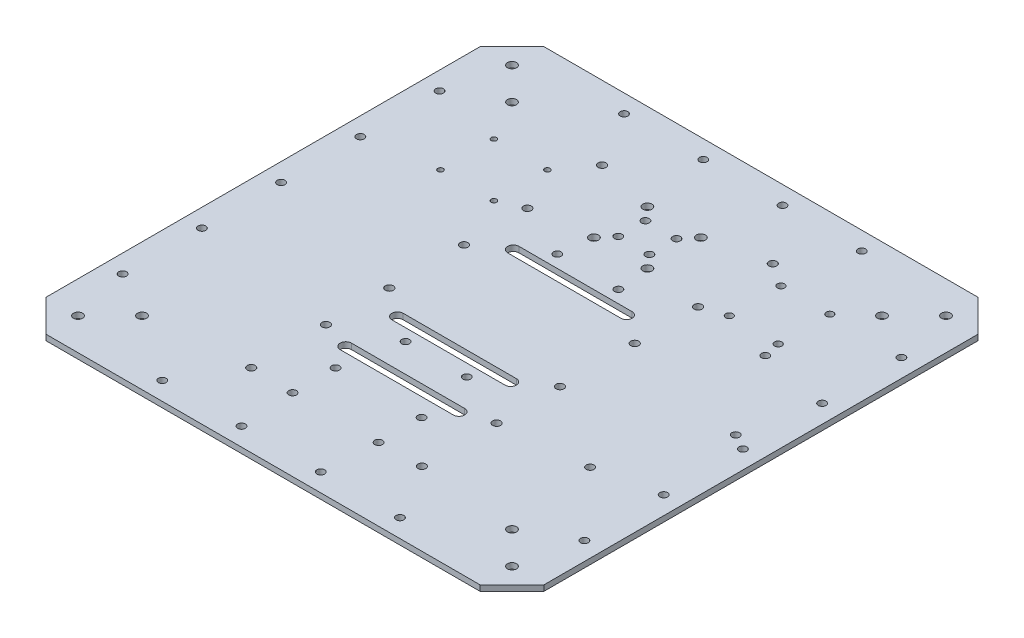
SolidWorks part; units mm, degrees
ref_plane "Front Plane" through (0, 0, 0) normal (0, 0, 1) x (1, 0, 0)
ref_plane "Top Plane" through (0, 0, 0) normal (0, 1, 0) x (1, 0, 0)
ref_plane "Right Plane" through (0, 0, 0) normal (1, 0, 0) x (0, 0, -1)
sketch "Sketch1" plane through (0, 0, 0) normal (0, 1, 0) x (1, 0, 0)
  line L0 (-160.4847, 61.5307) -> (-142.5242, 79.4912)
  line L1 (-160.4847, 79.4912) -> (118.9153, 79.4912)
  line L2 (-160.4847, 79.4912) -> (-160.4847, -199.9088)
  line L3 (-160.4847, -199.9088) -> (118.9153, -199.9088)
  line L4 (118.9153, 79.4912) -> (118.9153, -199.9088)
  line L5 (-20.7847, 79.4912) -> (-20.7847, -199.9088) construction
  line L6 (-160.4847, -60.2088) -> (118.9153, -60.2088) construction
  line L7 (118.9153, 61.5307) -> (100.9548, 79.4912)
  line L8 (118.9153, -181.9483) -> (100.9548, -199.9088)
  line L9 (-160.4847, -181.9483) -> (-142.5242, -199.9088)
  line L10 (-268.2478, 187.2542) -> (226.6783, -307.6719) construction
  line L11 (226.6783, -307.6719) -> (226.6783, 187.2542) construction
  line L12 (226.6783, 187.2542) -> (-268.2478, -307.6719) construction
  line L13 (-268.2478, -307.6719) -> (-268.2478, 187.2542) construction
  line L14 (-268.2478, 187.2542) -> (226.6783, 187.2542) construction
  line L15 (-268.2478, -307.6719) -> (226.6783, -307.6719) construction
  line L16 (-151.5045, 70.5109) -> (-268.2478, 187.2542) construction
  point P8 (-20.7847, 79.4912)
  point P11 (-160.4847, -60.2088)
  point P19 (118.9153, -60.2088)
  point P20 (-20.7847, -199.9088)
  point P22 (-151.5045, 70.5109)
  point P25 (-20.7847, -60.2088)
  point P26 (-20.7847, -60.2088)
  dimension "D1" = 279.4
  dimension "D2" = 279.4
  dimension "D3" = 165.1
  dimension "D4" = 25.4
extrude "Boss-Extrude1" add sketch "Sketch1" along normal blind 3.175 contours L2 L9 L3 L8 L4 L7 L1 L0 region at (-20.7847, 0, 60.2088)
sketch "Sketch2" plane through (0, 3.175, 0) normal (0, 1, 0) x (1, 0, 0)
  line L0 (-20.7847, 79.4912) -> (-20.7847, -287.8465) construction
  line L1 (-142.5242, 79.4912) -> (100.9548, 79.4912) construction
  line L2 (118.9153, -60.2088) -> (-158.2106, -60.2088) construction
  line L3 (118.9153, 61.5307) -> (118.9153, -181.9483) construction
  circle A0 centre (-38.0567, -17.5368) radius 2.159
  circle A1 centre (-3.7667, -17.5368) radius 2.159
  circle A2 centre (-38.0567, -102.6268) radius 2.159
  circle A3 centre (-3.7667, -102.6268) radius 2.159
  dimension "D5" = 4.318
  dimension "D6" = 4.318
  dimension "D7" = 4.318
  dimension "D8" = 4.318
  dimension "D1" = 17.272
  dimension "D2" = 34.29
  dimension "D3" = 85.09
  dimension "D4" = 42.672
extrude "Cut-Extrude1" cut sketch "Sketch2" against normal through all
sketch "Sketch4" plane through (0, 3.175, 0) normal (0, 1, 0) x (1, 0, 0)
  line L0 (-52.5347, -27.7088) -> (10.9653, -27.7088) construction
  line L1 (-52.5347, -24.5338) -> (10.9653, -24.5338)
  line L2 (-52.5347, -30.8838) -> (10.9653, -30.8838)
  line L3 (-52.5347, -92.7088) -> (10.9653, -92.7088) construction
  line L4 (-52.5347, -89.5338) -> (10.9653, -89.5338)
  line L5 (-52.5347, -95.8838) -> (10.9653, -95.8838)
  line L6 (118.9153, 61.5307) -> (118.9153, -181.9483) construction
  line L7 (-20.7847, -92.7088) -> (-20.7847, -198.1921) construction
  line L8 (-160.4847, -60.2088) -> (118.9153, -60.2088) construction
  line L9 (-160.4847, 61.5307) -> (-160.4847, -181.9483) construction
  line L14 (-52.5347, -121.708) -> (10.9653, -121.708) construction
  line L15 (-52.5347, -118.533) -> (10.9653, -118.533)
  line L16 (-52.5347, -124.883) -> (10.9653, -124.883)
  line L17 (-20.7847, -27.7088) -> (-20.7847, -92.7088) construction
  arc A0 (-52.5347, -24.5338) -> (-52.5347, -30.8838) centre (-52.5347, -27.7088) ccw
  arc A1 (10.9653, -30.8838) -> (10.9653, -24.5338) centre (10.9653, -27.7088) ccw
  arc A2 (-52.5347, -89.5338) -> (-52.5347, -95.8838) centre (-52.5347, -92.7088) ccw
  arc A3 (10.9653, -95.8838) -> (10.9653, -89.5338) centre (10.9653, -92.7088) ccw
  arc A7 (-52.5347, -118.533) -> (-52.5347, -124.883) centre (-52.5347, -121.708) ccw
  arc A8 (10.9653, -124.883) -> (10.9653, -118.533) centre (10.9653, -121.708) ccw
  point P2 (-20.7847, -27.7088)
  point P7 (-20.7847, -92.7088)
  point P18 (-20.7847, -60.2088)
  point P19 (-20.7847, -60.2088)
  point P33 (-20.7847, -121.708)
  dimension "D1" = 63.5
  dimension "D2" = 63.5
  dimension "D3" = 6.35
  dimension "D4" = 6.35
  dimension "D5" = 65
  dimension "D6" = 28.9992
  dimension "D8" = 63.5
  dimension "D9" = 6.35
extrude "Cut-Extrude2" cut sketch "Sketch4" against normal through all
sketch "Sketch7" plane through (0, 3.175, 0) normal (0, 1, 0) x (1, 0, 0)
  line L0 (-96.7307, 89.5196) -> (-96.7307, -24.0818) construction
  line L1 (-160.4847, -60.2088) -> (118.9153, -60.2088) construction
  line L2 (-160.4847, 61.5307) -> (-160.4847, -181.9483) construction
  line L3 (118.9153, 61.5307) -> (118.9153, -181.9483) construction
  line L4 (-20.7847, 79.4912) -> (-20.7847, -252.674) construction
  line L5 (-142.5242, 79.4912) -> (100.9548, 79.4912) construction
  circle A0 centre (-81.7447, 20.5632) radius 1.524
  circle A1 centre (-81.7447, -9.4088) radius 1.524
  circle A2 centre (-111.7167, -9.4088) radius 1.524
  circle A3 centre (-111.7167, 20.5632) radius 1.524
  dimension "D1" = 3.048
  dimension "D2" = 14.986
  dimension "D4" = 29.972
  dimension "D3" = 3.048
  dimension "D5" = 50.8
  dimension "D6" = 60.96
  dimension "D7" = 14.986
extrude "Cut-Extrude3" cut sketch "Sketch7" against normal through all
sketch "Sketch8" plane through (0, 3.175, 0) normal (0, 1, 0) x (1, 0, 0)
  line L0 (-142.5242, -199.9088) -> (100.9548, -199.9088) construction
  line L1 (118.9153, 61.5307) -> (118.9153, -181.9483) construction
  circle A0 centre (8.4253, -175.0168) radius 1.524
  circle A1 centre (8.4253, -144.5368) radius 1.524
  circle A2 centre (32.3013, -175.0168) radius 1.524
  circle A3 centre (32.3013, -144.5368) radius 1.524
  dimension "D1" = 3.048
  dimension "D2" = 30.48
  dimension "D3" = 23.876
  dimension "D4" = 24.892
  dimension "D5" = 86.614
extrude "Cut-Extrude4" [suppressed] cut sketch "Sketch8" against normal through all and the other way through all
sketch "Sketch10" plane through (0, 0, 0) normal (0, -1, 0) x (1, 0, 0)
  line L0 (-142.5242, 199.9088) -> (100.9548, 199.9088) construction
  line L1 (-20.7847, 199.9088) -> (-20.7847, 128.7119) construction
  line L2 (-52.5347, 124.883) -> (10.9653, 124.883) construction
  circle A0 centre (-44.9147, 159.173) radius 2.159
  circle A1 centre (3.3453, 159.173) radius 2.159
  circle A2 centre (-44.9147, 135.043) radius 2.159
  circle A3 centre (3.3453, 135.043) radius 2.159
  dimension "D1" = 4.318
  dimension "D2" = 48.26
  dimension "D4" = 10.16
  dimension "D6" = 4.318
  dimension "D7" = 4.318
  dimension "D8" = 4.318
  dimension "D3" = 24.13
  dimension "D5" = 24.13
extrude "Cut-Extrude6" cut sketch "Sketch10" against normal through all
sketch "Sketch9" plane through (0, 0, 0) normal (0, -1, 0) x (-1, 0, 0)
  line L1 (160.4847, -60.2088) -> (-327.4314, -60.2088) construction
  line L2 (-53.8913, -43.6513) -> (-53.8913, -126.5783) construction
  line L3 (20.7847, 79.4912) -> (20.7847, -331.7119) construction
  line L4 (142.5242, 79.4912) -> (-100.9548, 79.4912) construction
  line L7 (160.4847, 61.5307) -> (160.4847, -181.9483) construction
  circle A0 centre (-40.1753, 0.7512) radius 2.032
  circle A1 centre (-67.6073, 0.7512) radius 2.032
  circle A2 centre (-40.1753, 29.7072) radius 2.032
  circle A3 centre (-67.6073, 29.7072) radius 2.032
  dimension "D1" = 4.064
  dimension "D9" = 4.064
  dimension "D2" = 60.96
  dimension "D3" = 28.956
  dimension "D4" = 60.96
  dimension "D8" = 13.716
extrude "Cut-Extrude5" cut sketch "Sketch9" against normal through all
sketch "Sketch13" plane through (0, 0, 0) normal (0, -1, 0) x (1, 0, 0)
  line L0 (-20.7847, -79.4912) -> (-20.7847, 261.4711) construction
  line L1 (-142.5242, -79.4912) -> (100.9548, -79.4912) construction
  line L2 (-160.4847, 60.2088) -> (239.2508, 60.2088) construction
  line L3 (-160.4847, -61.5307) -> (-160.4847, 181.9483) construction
  line L4 (-35.7847, -30.7512) -> (-35.7847, -0.7512) construction
  line L5 (-35.7847, -15.7512) -> (8.2736, -15.7512) construction
  circle A0 centre (-35.7847, -0.7512) radius 2.54
  circle A1 centre (-35.7847, -30.7512) radius 2.54
  circle A2 centre (-5.7847, -30.7512) radius 2.54
  circle A3 centre (-5.7847, -0.7512) radius 2.54
  circle A4 centre (-29.5178, -23.3712) radius 2.159
  circle A5 centre (-29.5178, -8.1312) radius 2.159
  circle A6 centre (-12.0517, -8.1312) radius 2.159
  circle A7 centre (-12.0517, -23.3712) radius 2.159
  dimension "D1" = 5.08
  dimension "D2" = 5.08
  dimension "D6" = 4.318
  dimension "D7" = 15.24
  dimension "D3" = 30
  dimension "D4" = 15
  dimension "D5" = 60.96
extrude "Cut-Extrude8" cut sketch "Sketch13" against normal through all
sketch "Sketch14" plane through (0, 0, 0) normal (0, -1, 0) x (1, 0, 0)
  line L0 (-20.7847, 199.9088) -> (-20.7847, -154.5354) construction
  line L1 (-142.5242, 199.9088) -> (100.9548, 199.9088) construction
  line L2 (-160.4847, 60.2088) -> (331.9066, 60.2088) construction
  line L3 (-160.4847, -61.5307) -> (-160.4847, 181.9483) construction
  line L4 (-160.4847, 181.9483) -> (-142.5242, 199.9088) construction
  line L5 (-268.2478, -187.2542) -> (226.6783, 307.6719) construction
  line L6 (-268.2478, -187.2542) -> (226.6783, -187.2542) construction
  line L7 (-268.2478, -187.2542) -> (-268.2478, 307.6719) construction
  line L8 (-160.4847, 181.9483) -> (-142.5242, 199.9088) construction
  line L9 (-151.5045, 190.9286) -> (-83.1439, 122.568) construction
  line L10 (-268.2478, 307.6719) -> (226.6783, 307.6719) construction
  line L11 (226.6783, -187.2542) -> (226.6783, 307.6719) construction
  line L12 (226.6783, -187.2542) -> (-268.2478, 307.6719) construction
  line L14 (-160.4847, -61.5307) -> (-142.5242, -79.4912) construction
  line L21 (-268.2478, -187.2542) -> (-151.5045, -70.5109) construction
  line L22 (109.935, -70.5109) -> (226.6783, -187.2542) construction
  line L23 (118.9153, -61.5307) -> (100.9548, -79.4912) construction
  line L24 (109.935, 190.9286) -> (226.6783, 307.6719) construction
  line L25 (118.9153, 181.9483) -> (100.9548, 199.9088) construction
  line L26 (-268.2478, 307.6719) -> (-151.5045, 190.9286) construction
  circle A1 centre (-142.5242, 181.9483) radius 2.54
  circle A3 centre (-124.5637, 163.9878) radius 2.54
  circle A4 centre (82.9942, 163.9878) radius 2.54
  circle A7 centre (100.9548, 181.9483) radius 2.54
  circle A8 centre (-142.5242, -61.5307) radius 2.54
  circle A11 centre (-124.5637, -43.5701) radius 2.54
  circle A14 centre (100.9548, -61.5307) radius 2.54
  circle A15 centre (82.9942, -43.5701) radius 2.54
  point P8 (-20.7847, 60.2088)
  point P30 (226.6783, 60.2088)
  point P33 (-151.5045, -70.5109)
  point P36 (-20.7847, -187.2542)
  dimension "D3" = 5.08
  dimension "D6" = 5.08
  dimension "D1" = 12.7
  dimension "D2" = 165.1
  dimension "D9" = 25.4
extrude "Cut-Extrude9" cut sketch "Sketch14" against normal through all
sketch "Sketch15" plane through (0, 0, 0) normal (0, -1, 0) x (1, 0, 0)
  line L0 (-20.7847, 199.9088) -> (-20.7847, 125.875) construction
  line L1 (-142.5242, 199.9088) -> (100.9548, 199.9088) construction
  line L2 (-160.4847, 60.2088) -> (75.4631, 60.2088) construction
  line L3 (-160.4847, -61.5307) -> (-160.4847, 181.9483) construction
  circle A0 centre (-43.0097, 189.7488) radius 2.159
  circle A1 centre (-87.4597, 189.7488) radius 2.159
  circle A2 centre (-150.3247, 60.2088) radius 2.159
  circle A3 centre (-150.3247, 104.6588) radius 2.159
  circle A4 centre (-150.3247, 149.1088) radius 2.159
  circle A5 centre (108.7553, 149.1088) radius 2.159
  circle A6 centre (108.7553, 104.6588) radius 2.159
  circle A7 centre (108.7553, 60.2088) radius 2.159
  circle A8 centre (45.8903, 189.7488) radius 2.159
  circle A9 centre (1.4403, 189.7488) radius 2.159
  circle A10 centre (1.4403, -69.3312) radius 2.159
  circle A11 centre (45.8903, -69.3312) radius 2.159
  circle A12 centre (108.7553, 15.7588) radius 2.159
  circle A13 centre (108.7553, -28.6912) radius 2.159
  circle A14 centre (-150.3247, -28.6912) radius 2.159
  circle A15 centre (-150.3247, 15.7588) radius 2.159
  circle A16 centre (-87.4597, -69.3312) radius 2.159
  circle A17 centre (-43.0097, -69.3312) radius 2.159
  dimension "D3" = 4.318
  dimension "D4" = 4.318
  dimension "D8" = 4.318
  dimension "D9" = 4.318
  dimension "D10" = 4.318
  dimension "D1" = 22.225
  dimension "D2" = 44.45
  dimension "D5" = 10.16
  dimension "D6" = 44.45
  dimension "D7" = 44.45
  dimension "D11" = 10.16
extrude "Cut-Extrude10" cut sketch "Sketch15" against normal through all
sketch "Sketch16" plane through (0, 0, 0) normal (0, -1, 0) x (-1, 0, 0)
  line L0 (20.7847, 79.4912) -> (20.7847, -323.0503) construction
  line L1 (-49.3193, -101.9918) -> (-89.9593, -101.9918)
  line L2 (-49.3193, -101.9918) -> (-49.3193, -18.4258)
  line L3 (-49.3193, -18.4258) -> (-89.9593, -18.4258)
  line L4 (-89.9593, -101.9918) -> (-89.9593, -18.4258)
  line L6 (142.5242, 79.4912) -> (-100.9548, 79.4912) construction
  line L7 (160.4847, -60.2088) -> (-312.3855, -60.2088) construction
  line L8 (160.4847, 61.5307) -> (160.4847, -181.9483) construction
  circle A0 centre (-74.7193, -111.8978) radius 2.159
  circle A1 centre (-69.6393, -8.5198) radius 2.159
  circle A2 centre (-99.8653, -55.3418) radius 2.159
  point P18 (-89.9593, -60.2088)
  dimension "D3" = 9.906
  dimension "D4" = 9.906
  dimension "D5" = 9.906
  dimension "D6" = 15.24
  dimension "D7" = 20.32
  dimension "D8" = 46.65
  dimension "D9" = 4.318
  dimension "D10" = 4.318
  dimension "D11" = 4.318
  dimension "D1" = 83.566
  dimension "D2" = 40.64
  dimension "D12" = 120.65
  dimension "D13" = 0
extrude "Cut-Extrude11" cut sketch "Sketch16" against normal through all contours A2 | A0 | A1
sketch "Sketch17" plane through (0, 3.175, 0) normal (0, 1, 0) x (1, 0, 0)
  line L2 (-20.7847, 79.4912) -> (-20.7847, -395.818) construction
  line L3 (-142.5242, 79.4912) -> (100.9548, 79.4912) construction
  line L4 (118.9153, -60.2088) -> (-127.1454, -60.2088) construction
  line L5 (118.9153, 61.5307) -> (118.9153, -181.9483) construction
  circle A12 centre (27.0943, -158.6338) radius 2.2225
  circle A13 centre (-68.6637, -158.6338) radius 2.2225
  circle A14 centre (27.0943, -116.7238) radius 2.2225
  circle A15 centre (-68.6637, -116.7238) radius 2.2225
  circle A16 centre (27.0943, -81.1638) radius 2.2225
  circle A17 centre (-68.6637, -81.1638) radius 2.2225
  circle A18 centre (27.0943, -39.2538) radius 2.2225
  circle A19 centre (-68.6637, -39.2538) radius 2.2225
  circle A20 centre (27.0943, -3.6938) radius 2.2225
  circle A21 centre (-68.6637, -3.6938) radius 2.2225
  circle A22 centre (27.0943, 38.2162) radius 2.2225
  circle A23 centre (-68.6637, 38.2162) radius 2.2225
  circle A24 centre (-68.6637, 38.2162) radius 2.2225
  circle A25 centre (27.0943, 38.2162) radius 2.2225
  circle A26 centre (-68.6637, -3.6938) radius 2.2225
  circle A27 centre (27.0943, -3.6938) radius 2.2225
  circle A28 centre (-68.6637, -39.2538) radius 2.2225
  circle A29 centre (27.0943, -39.2538) radius 2.2225
  circle A30 centre (-68.6637, -81.1638) radius 2.2225
  circle A31 centre (27.0943, -81.1638) radius 2.2225
  circle A32 centre (-68.6637, -116.7238) radius 2.2225
  circle A33 centre (27.0943, -116.7238) radius 2.2225
  circle A34 centre (-68.6637, -158.6338) radius 2.2225
  dimension "D1" = 4.445
  dimension "D2" = 4.445
  dimension "D3" = 4.445
  dimension "D4" = 4.445
  dimension "D5" = 4.445
  dimension "D6" = 4.445
  dimension "D7" = 4.445
  dimension "D8" = 4.445
  dimension "D9" = 4.445
  dimension "D10" = 4.445
  dimension "D11" = 4.445
  dimension "D12" = 4.445
  dimension "D25" = 56.515
  dimension "D24" = 56.515
  dimension "D13" = 95.758
  dimension "D14" = 41.91
  dimension "D15" = 95.758
  dimension "D16" = 41.91
  dimension "D17" = 95.758
  dimension "D18" = 41.91
  dimension "D19" = 47.879
  dimension "D20" = 47.879
  dimension "D21" = 47.879
  dimension "D22" = 20.955
extrude "Cut-Extrude13" cut sketch "Sketch17" against normal through all contours A23 | A22 | A20 | A21 | A18 | A19 | A17 | A16 | A12 | A14 | A15 | A13
sketch "Sketch18" [suppressed] plane through (0, 3.175, 0) normal (0, 1, 0) x (1, 0, 0)
  line L1 (-142.5242, -199.9088) -> (-160.4847, -181.9483)
  line L2 (-142.5242, -199.9088) -> (-106.6032, -163.9878)
  line L3 (-106.6032, -163.9878) -> (-124.5637, -146.0273)
  line L4 (-160.4847, -181.9483) -> (-124.5637, -146.0273)
  line L5 (-20.7847, 79.4912) -> (-20.7847, -264.9481) construction
  line L6 (-142.5242, 79.4912) -> (100.9548, 79.4912) construction
  line L7 (118.9153, -60.2088) -> (-155.4453, -60.2088) construction
  line L8 (118.9153, 61.5307) -> (118.9153, -181.9483) construction
  line L9 (-160.4847, 61.5307) -> (-124.5637, 25.6096)
  line L10 (-106.6032, 43.5701) -> (-124.5637, 25.6096)
  line L11 (-142.5242, 79.4912) -> (-106.6032, 43.5701)
  line L12 (-142.5242, 79.4912) -> (-160.4847, 61.5307)
  line L13 (100.9548, 79.4912) -> (118.9153, 61.5307)
  line L14 (100.9548, 79.4912) -> (65.0337, 43.5701)
  line L15 (65.0337, 43.5701) -> (82.9942, 25.6096)
  line L16 (118.9153, 61.5307) -> (82.9942, 25.6096)
  line L17 (118.9153, -181.9483) -> (82.9942, -146.0273)
  line L18 (65.0337, -163.9878) -> (82.9942, -146.0273)
  line L19 (100.9548, -199.9088) -> (65.0337, -163.9878)
  line L20 (100.9548, -199.9088) -> (118.9153, -181.9483)
  line L21 (-142.5242, -181.9483) -> (-124.5637, -163.9878) construction
  line L22 (-160.4847, -181.9483) -> (-142.5242, -199.9088) construction
  line L23 (-160.4847, -181.9483) -> (-142.5242, -199.9088) construction
  circle A2 centre (-124.5637, -163.9878) radius 2.54 construction
  circle A3 centre (-142.5242, -181.9483) radius 2.54 construction
  circle A4 centre (-124.5637, -163.9878) radius 2.54 construction
  circle A5 centre (-142.5242, -181.9483) radius 2.54 construction
  point P12 (-151.5045, -190.9286)
  point P33 (-151.5045, -190.9286)
  dimension "D1" = 50.8
  dimension "D2" = 25.4
